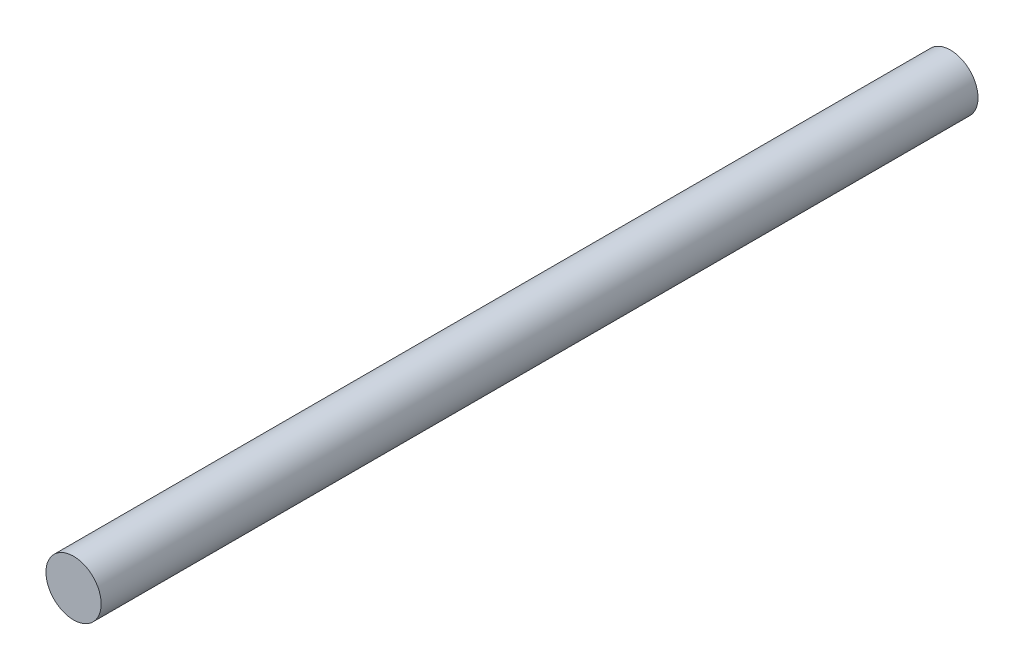
SolidWorks part; units mm, degrees
ref_plane "Front Plane" through (0, 0, 0) normal (0, 0, 1) x (1, 0, 0)
ref_plane "Top Plane" through (0, 0, 0) normal (0, 1, 0) x (1, 0, 0)
ref_plane "Right Plane" through (0, 0, 0) normal (1, 0, 0) x (0, 0, -1)
sketch "Sketch1" plane through (0, 0, 0) normal (0, 0, 1) x (1, 0, 0)
  circle A0 centre (0, 0) radius 4
  dimension "D1" = 8
extrude "Boss-Extrude1" add sketch "Sketch1" along normal mid plane 127
